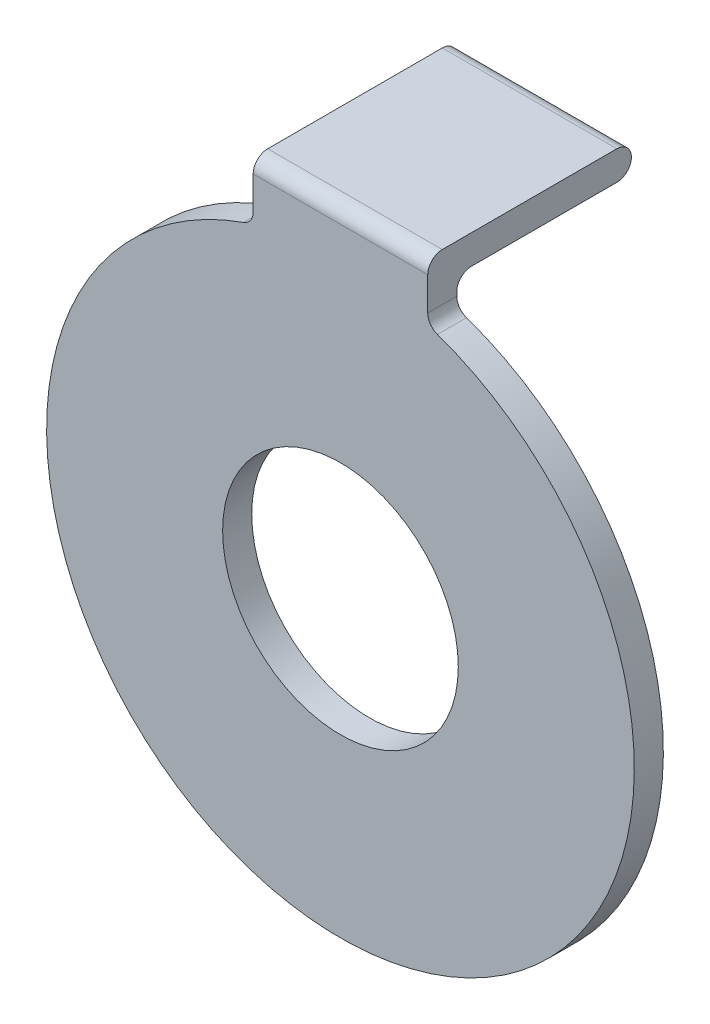
SolidWorks part; units mm, degrees
material "AISI 1020"
ref_plane "Płaszczyzna XY" through (0, 0, 0) normal (0, 0, 1) x (1, 0, 0)
ref_plane "Płaszczyzna XZ" through (0, 0, 0) normal (0, 1, 0) x (1, 0, 0)
ref_plane "Płaszczyzna YZ" through (0, 0, 0) normal (1, 0, 0) x (0, 0, -1)
sketch "Szkic1" plane through (0, 0, 0) normal (0, 0, 1) x (1, 0, 0)
  line L0 (0, -14.904) -> (0, 14.904) construction
  line L18 (3, 11.6442) -> (-3, 11.6442)
  line L19 (3, 11.6442) -> (3, 9.6442)
  line L21 (-3, 11.6442) -> (-3, 9.6442)
  circle A1 centre (0, 0) radius 4.05
  arc A2 (-3, 9.6442) -> (3, 9.6442) centre (0, 0) ccw
  point P1 (0, 10.1)
  point P5 (0, 9.35)
  point P6 (0, 11.5122)
  point P7 (0, 0)
  point P8 (0, 0)
  point P9 (0, 0)
  point P12 (0, 0)
  dimension "D1" = 8.1
  dimension "D2" = 20.2
  dimension "D3" = 6
  dimension "D4" = 2
  dimension "D5" = 2
extrude "Dodanie-wyciągnięcie3" add sketch "Szkic1" along normal blind 1 contours A2 A1 | A2 region at (2.7032, 10.6442, 0)
sketch "Szkic5" plane through (0, 0, 0) normal (0, 0, -1) x (-1, 0, 0)
  line L0 (3, 11.6442) -> (3, 9.6442) construction
  line L1 (-3, 11.6442) -> (3, 11.6442)
  line L2 (-3, 11.6442) -> (-3, 10.6442)
  line L3 (-3, 10.6442) -> (3, 10.6442)
  line L4 (3, 11.6442) -> (3, 10.6442)
  dimension "D1" = 1
extrude "Dodanie-wyciągnięcie5" add sketch "Szkic5" along normal blind 6
fillet "Zaokrąglenie3" radius 0.5 6 edges at (-3, 9.6442, 0.5) (3, 9.6442, 0.5) (0, 11.6442, -6) (0, 10.6442, -6) (0, 10.6442, 0) (0, 11.6442, 1)
